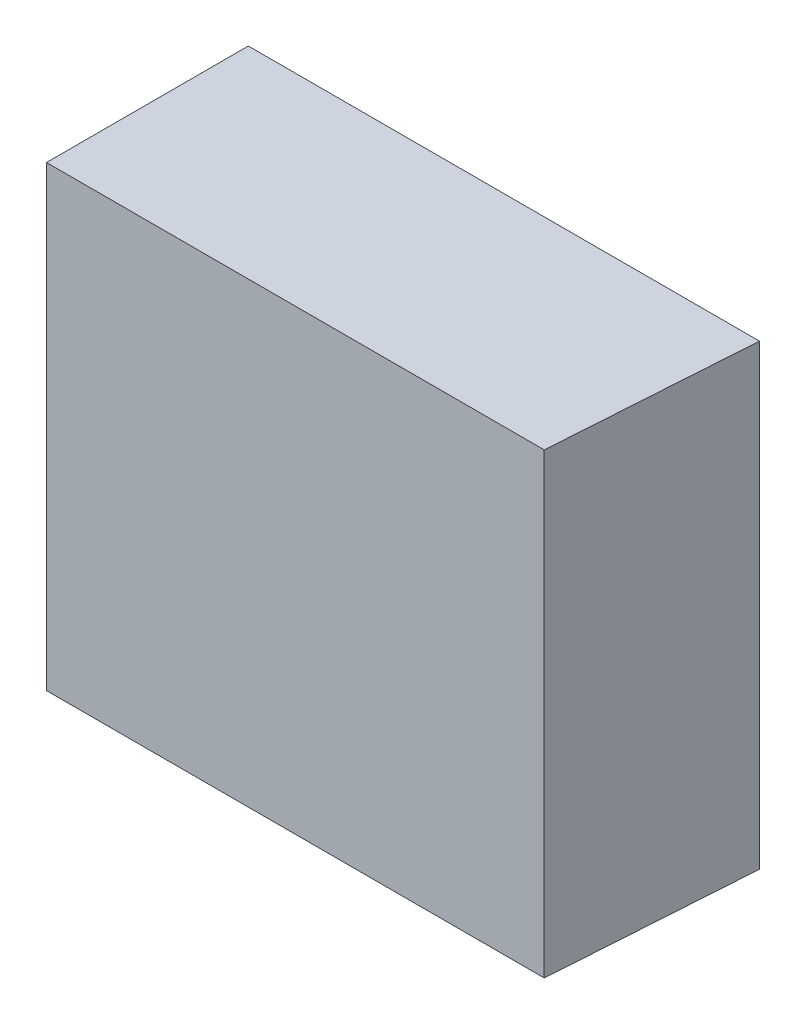
SolidWorks part; units mm, degrees
ref_plane "前视基准面" through (0, 0, 0) normal (0, 0, 1) x (1, 0, 0)
ref_plane "上视基准面" through (0, 0, 0) normal (0, 1, 0) x (1, 0, 0)
ref_plane "右视基准面" through (0, 0, 0) normal (1, 0, 0) x (0, 0, -1)
other "Configuration Table"
sketch "草图1" plane through (0, 0, 0) normal (0, 1, 0) x (1, 0, 0)
  line L5 (230, 0) -> (0, 0)
  line L7 (-150, -150) -> (220, -150)
  line L8 (220, -150) -> (230, 0)
  line L10 (-150, -150) -> (-150, 0)
  line L11 (0, 0) -> (-150, 0)
  point P0 (0, 0)
  dimension "D1" = 380
  dimension "D2" = 150
  dimension "D3" = 370
extrude "凸台-拉伸2" add sketch "草图1" along normal mid plane 340 contours L5 L11 L10 L7 L8
shell "抽壳2" thickness 4 removed face at (40, 0, 0)
